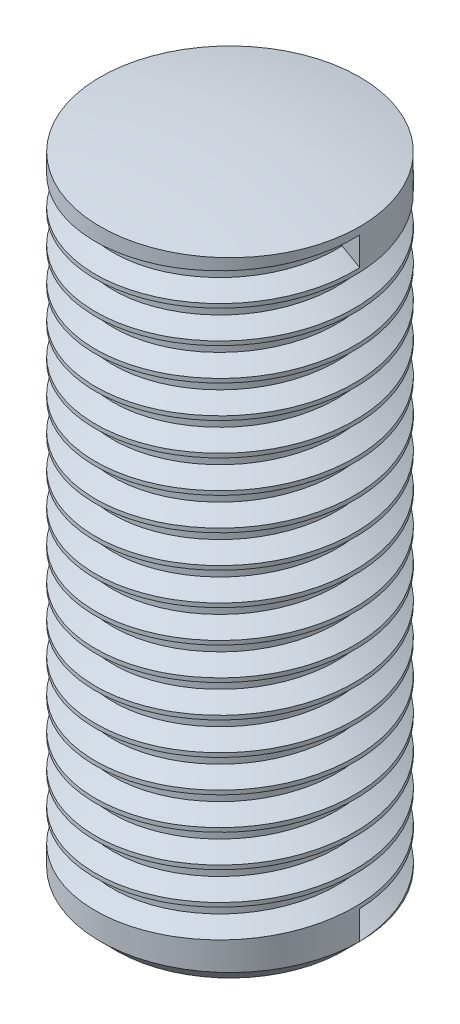
SolidWorks part; units mm, degrees
material "AISI 1045 钢，冷拔"
ref_plane "前视基准面" through (0, 0, 0) normal (0, 0, 1) x (1, 0, 0)
ref_plane "上视基准面" through (0, 0, 0) normal (0, 1, 0) x (1, 0, 0)
ref_plane "右视基准面" through (0, 0, 0) normal (1, 0, 0) x (0, 0, -1)
sketch "草图1" plane through (0, 0, 0) normal (0, 0, 1) x (1, 0, 0)
  line L0 (0, 7.3438) -> (0, 27.3438)
  line L1 (0, 27.3438) -> (5, 27.3438) construction
  line L2 (0, 7.3438) -> (4, 7.3438)
  line L3 (4, 7.3438) -> (4, 26.9397)
  arc A0 (4, 26.9397) -> (0, 27.3438) centre (0, 7.3438) ccw
  dimension "D3" = 20
  dimension "D1" = 4
  dimension "D2" = 20
revolve "旋转1" add sketch "草图1" angle 360 about L0
chamfer "倒角1" distance 0.5 angle 45 1 edges at (0, 7.3438, -4)
thread "螺纹线1" pitch 1 method cut trim with start face yes trim with end face yes profile "螺纹线轮廓1" start angle 0, offset 0, length 18, pitch 1, diameter 8
ref_plane "基准面1" through (4, 7.8438, 0) normal (0, 0, 1) x (1, 0, 0)
sketch "螺纹线轮廓1" plane through (4, 7.8438, 0) normal (0, 0, 1) x (1, 0, 0)
  line L0 (0, 0) -> (0, 1) construction
  line L11 (0, 0) -> (0, 0.875)
  line L12 (0, 0.875) -> (-0.5413, 0.5625)
  line L13 (-0.5413, 0.5625) -> (-0.5413, 0.3125)
  line L15 (-0.5413, 0.3125) -> (0, 0)
  line L17 (-0.5413, 0.4375) -> (0, 0.4375) construction
  point P2 (0, 0)
  dimension "Pitch" = 1
  dimension "Profile_Angle" = 60
  dimension "Profile_Land" = 0.25
  dimension "Profile_Height" = 0.5413
